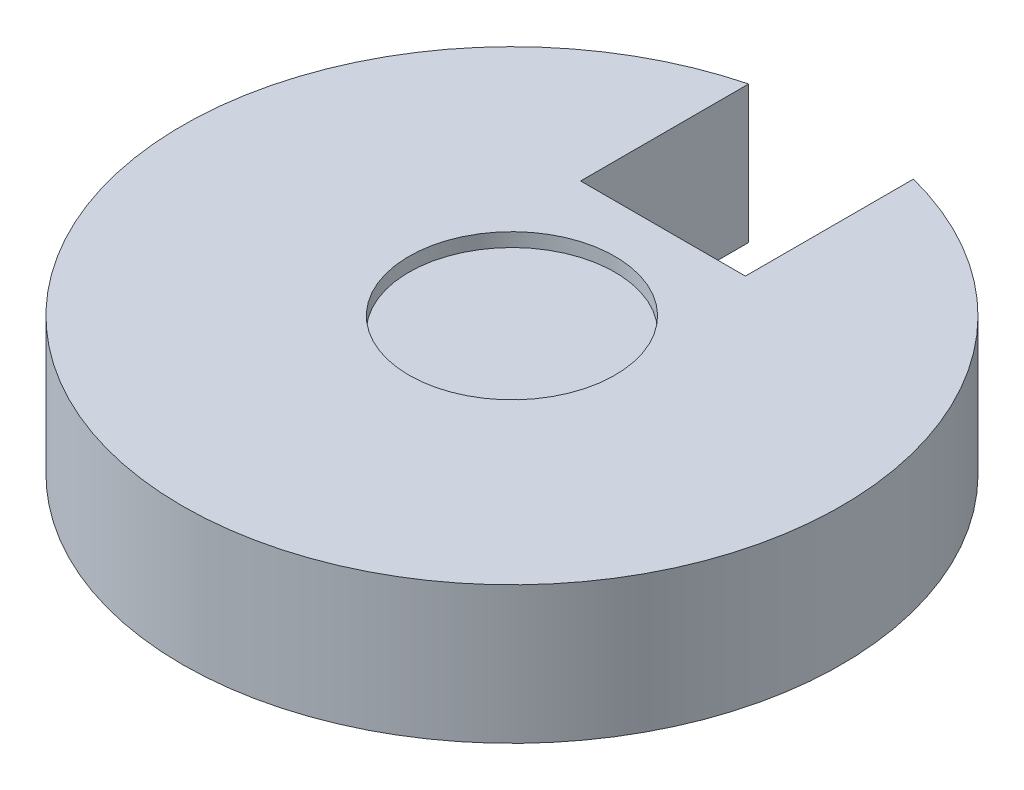
SolidWorks part; units mm, degrees
ref_plane "Front Plane" through (0, 0, 0) normal (0, 0, 1) x (1, 0, 0)
ref_plane "Top Plane" through (0, 0, 0) normal (0, 1, 0) x (1, 0, 0)
ref_plane "Right Plane" through (0, 0, 0) normal (1, 0, 0) x (0, 0, -1)
sketch "Sketch1" plane through (0, 0, 0) normal (0, 1, 0) x (1, 0, 0)
  line L0 (0, 0) -> (0, 17) construction
  line L1 (-6, 23) -> (-6, 23.2379)
  line L2 (6, 11) -> (-6, 11)
  line L3 (6, 11) -> (6, 23)
  line L5 (-6, 11) -> (-6, 23)
  line L6 (6, 11) -> (-6, 23) construction
  line L7 (6, 23) -> (-6, 11) construction
  line L8 (6, 23) -> (6, 23.2379)
  line L9 (0, 0) -> (0, -24)
  circle A1 centre (0, 0) radius 7.5
  arc A2 (-6, 23.2379) -> (6, 23.2379) centre (0, 0) ccw
  dimension "D2" = 15
  dimension "D3" = 17
  dimension "D4" = 12
  dimension "D5" = 12
extrude "Boss-Extrude1" add sketch "Sketch1" along normal blind 10 contours A2 L8 L3 L2 L5 L1 A1 region at (-6.6735, 0, -17)
extrude "Boss-Extrude2" add sketch "Sketch1<3>" along normal blind 9 contours A1 region at (-5.1533, 0, -5.1533)
sketch "Sketch1<3>" plane through (0, 0, 0) normal (0, 1, 0) x (1, 0, 0) same geometry as "Sketch1"
